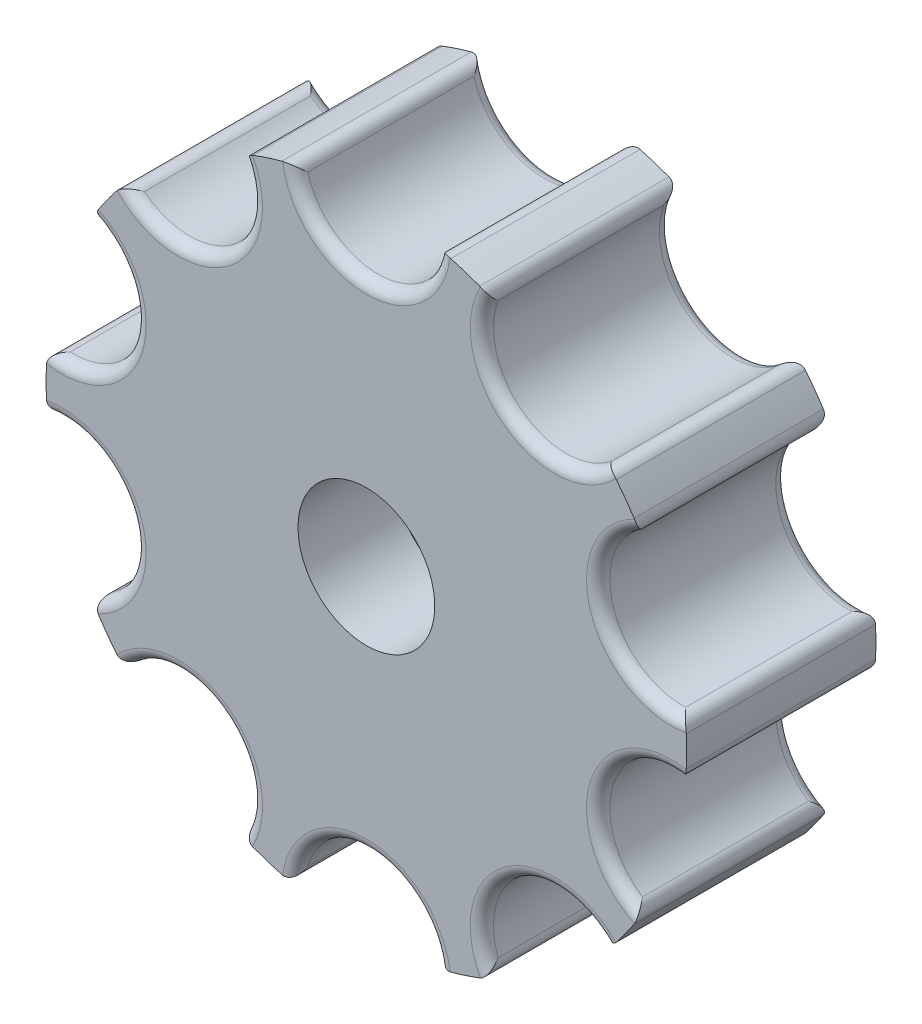
SolidWorks part; units mm, degrees
ref_plane "Front Plane" through (0, 0, 0) normal (0, 0, 1) x (1, 0, 0)
ref_plane "Top Plane" through (0, 0, 0) normal (0, 1, 0) x (1, 0, 0)
ref_plane "Right Plane" through (0, 0, 0) normal (1, 0, 0) x (0, 0, -1)
sketch "Sketch1" plane through (0, 0, 0) normal (0, 0, 1) x (1, 0, 0)
  circle A0 centre (0, 0) radius 11
  circle A1 centre (0, 0) radius 2.35
  dimension "D1" = 22
extrude "Boss-Extrude1" add sketch "Sketch1" along normal blind 6.5
sketch "Sketch2" plane through (0, 0, 6.5) normal (0, 0, 1) x (1, 0, 0)
  circle A0 centre (0, -11) radius 2.5
  circle A1 centre (0, 0) radius 11 construction
  circle A2 centre (-6.4656, -8.8992) radius 2.5
  circle A3 centre (-10.4616, -3.3992) radius 2.5
  circle A4 centre (-10.4616, 3.3992) radius 2.5
  circle A5 centre (-6.4656, 8.8992) radius 2.5
  circle A6 centre (0, 11) radius 2.5
  circle A7 centre (6.4656, 8.8992) radius 2.5
  circle A8 centre (10.4616, 3.3992) radius 2.5
  circle A9 centre (10.4616, -3.3992) radius 2.5
  circle A10 centre (6.4656, -8.8992) radius 2.5
  point P22 (0, 0)
  dimension "D1" = 5
  dimension "D2" = 10
extrude "Cut-Extrude1" cut sketch "Sketch2" against normal blind 7.5
fillet "Fillet1" radius 0.4 40 edges at (-9.4239, 5.6736, 3.25) (-8.084, 2.6266, 6.5) (-10.959, 0.9492, 3.25) (-8.084, 2.6266, 0) (-4.2892, 10.1293, 3.25) (-4.9962, 6.8766, 6.5) (-8.3081, 7.2094, 3.25) (-4.9962, 6.8766, 0) (2.4838, 10.7159, 3.25) (0, 8.5, 6.5) (-2.4838, 10.7159, 3.25) (0, 8.5, 0) (10.959, 0.9492, 3.25) (8.084, 2.6266, 6.5) (9.4239, 5.6736, 3.25) (8.084, 2.6266, 0) (9.4239, -5.6736, 3.25) (8.084, -2.6266, 6.5) (10.959, -0.9492, 3.25) (8.084, -2.6266, 0) (4.2892, -10.1293, 3.25) (4.9962, -6.8766, 6.5) (8.3081, -7.2094, 3.25) (4.9962, -6.8766, 0) (8.3081, 7.2094, 3.25) (4.9962, 6.8766, 6.5) (4.2892, 10.1293, 3.25) (4.9962, 6.8766, 0) (-2.4838, -10.7159, 3.25) (0, -8.5, 6.5) (2.4838, -10.7159, 3.25) (0, -8.5, 0) (-8.3081, -7.2094, 3.25) (-4.9962, -6.8766, 6.5) (-4.2892, -10.1293, 3.25) (-4.9962, -6.8766, 0) (-10.959, -0.9492, 3.25) (-8.084, -2.6266, 6.5) (-9.4239, -5.6736, 3.25) (-8.084, -2.6266, 0)
sketch "Sketch3" plane through (0, 0, 0) normal (0, 0, -1) x (-1, 0, 0)
  line L1 (4.3301, 0) -> (2.1651, 3.75)
  line L2 (2.1651, 3.75) -> (-2.1651, 3.75)
  line L3 (-2.1651, 3.75) -> (-4.3301, 0)
  line L4 (-4.3301, 0) -> (-2.1651, -3.75)
  line L5 (-2.1651, -3.75) -> (2.1651, -3.75)
  line L6 (2.1651, -3.75) -> (4.3301, 0)
  circle A0 centre (0, 0) radius 3.75 construction
  dimension "D1" = 7.5
extrude "Cut-Extrude2" cut sketch "Sketch3" against normal blind 3.2
